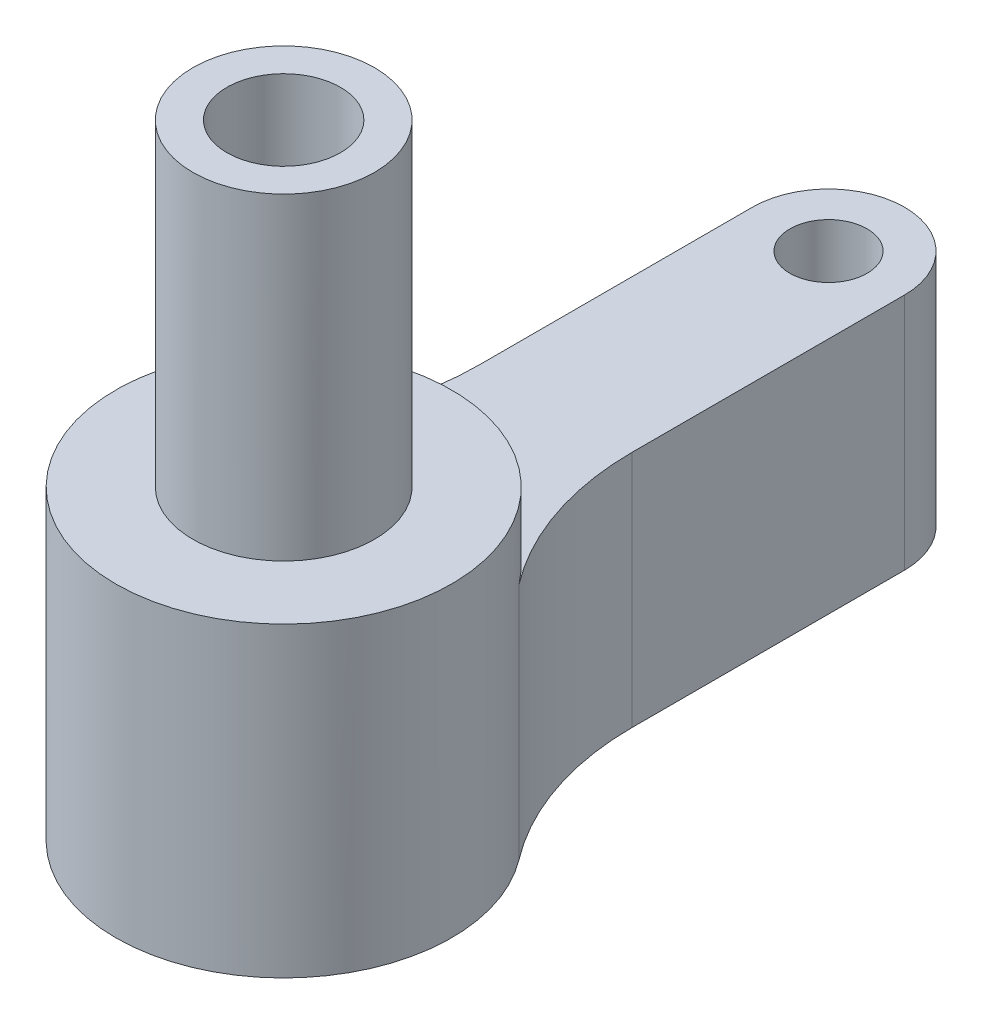
SolidWorks part; units mm, degrees
ref_plane "Front Plane" through (0, 0, 0) normal (0, 0, 1) x (1, 0, 0)
ref_plane "Top Plane" through (0, 0, 0) normal (0, 1, 0) x (1, 0, 0)
ref_plane "Right Plane" through (0, 0, 0) normal (1, 0, 0) x (0, 0, -1)
other "Configuration Table"
sketch "Sketch1" plane through (0, 0, 0) normal (0, 1, 0) x (1, 0, 0)
  line L0 (0, 0) -> (0, 7.4) construction
  line L1 (-3.35, 24) -> (-3.35, 12)
  line L2 (3.35, 24) -> (3.35, 12)
  line L3 (-3.35, 6.5983) -> (-3.35, 0) construction
  line L4 (0, 7.4) -> (0, 24) construction
  line L5 (3.35, 6.5983) -> (3.35, 0) construction
  line L6 (3.35, 12) -> (3.35, 6.5983) construction
  line L7 (-3.35, 12) -> (-3.35, 6.5983) construction
  arc A0 (-5.8866, 4.4842) -> (5.8866, 4.4842) centre (0, 0) ccw
  arc A1 (-3.35, 24) -> (3.35, 24) centre (0, 24) cw
  arc A2 (-3.35, 0) -> (3.35, 0) centre (0, 0) ccw construction
  arc A3 (-5.8866, 4.4842) -> (-3.35, 12) centre (-15.7528, 12) ccw
  arc A4 (5.8866, 4.4842) -> (3.35, 12) centre (15.7528, 12) cw
  arc A5 (-3.35, 6.5983) -> (-5.8866, 4.4842) centre (0, 0) ccw construction
  arc A6 (0, 7.4) -> (-3.35, 6.5983) centre (0, 0) ccw construction
  arc A7 (3.35, 6.5983) -> (0, 7.4) centre (0, 0) ccw construction
  arc A8 (5.8866, 4.4842) -> (3.35, 6.5983) centre (0, 0) ccw construction
  circle A9 centre (0, 24) radius 1.7
  point P16 (-0.2182, 24)
  dimension "D1" = 6.7
  dimension "D3" = 12.4028
  dimension "D4" = 24
  dimension "D2" = 14.8
  dimension "D5" = 12
  dimension "D6" = 3.4
extrude "Boss-Extrude1" add sketch "Sketch1" along normal blind 6.75 and the other way blind 6.75
sketch "Sketch2" plane through (0, 6.75, 0) normal (0, 1, 0) x (1, 0, 0)
  circle A0 centre (0, 0) radius 4
  dimension "D1" = 8
extrude "Boss-Extrude2" add sketch "Sketch2" along normal blind 14
sketch "Sketch3" plane through (0, 20.75, 0) normal (0, 1, 0) x (1, 0, 0)
  circle A0 centre (0, 0) radius 2.5
  dimension "D1" = 5
extrude "Cut-Extrude1" cut sketch "Sketch3" against normal blind 5
sketch "Sketch4" plane through (0, 15.75, 0) normal (0, 1, 0) x (1, 0, 0)
  circle A0 centre (0, 0) radius 1.7
  dimension "D1" = 3.4
extrude "Cut-Extrude2" cut sketch "Sketch4" against normal offset from surface (17.5 mm away) 5 up to face at (0, -6.75, -22.3)
sketch "Sketch5" plane through (0, 6.75, 0) normal (0, 1, 0) x (1, 0, 0)
  line L0 (3.35, 12) -> (3.35, 24) construction
  line L1 (-3.35, 24) -> (-3.35, 12) construction
  line L2 (3.35, 12) -> (3.35, 24)
  line L3 (-3.35, 24) -> (-3.35, 12)
  arc A0 (5.8866, 4.4842) -> (-5.8866, 4.4842) centre (0, 0) ccw
  arc A1 (3.35, 12) -> (5.8866, 4.4842) centre (15.7528, 12) ccw construction
  arc A2 (3.35, 24) -> (-3.35, 24) centre (0, 24) ccw construction
  arc A3 (-5.8866, 4.4842) -> (-3.35, 12) centre (-15.7528, 12) ccw construction
  arc A4 (3.35, 12) -> (5.8866, 4.4842) centre (15.7528, 12) ccw
  arc A5 (3.35, 24) -> (-3.35, 24) centre (0, 24) ccw
  arc A6 (-5.8866, 4.4842) -> (-3.35, 12) centre (-15.7528, 12) ccw
  arc A7 (-5.8866, 4.4842) -> (5.8866, 4.4842) centre (0, 0) ccw construction
extrude "Cut-Extrude4" cut sketch "Sketch5" against normal blind 3
